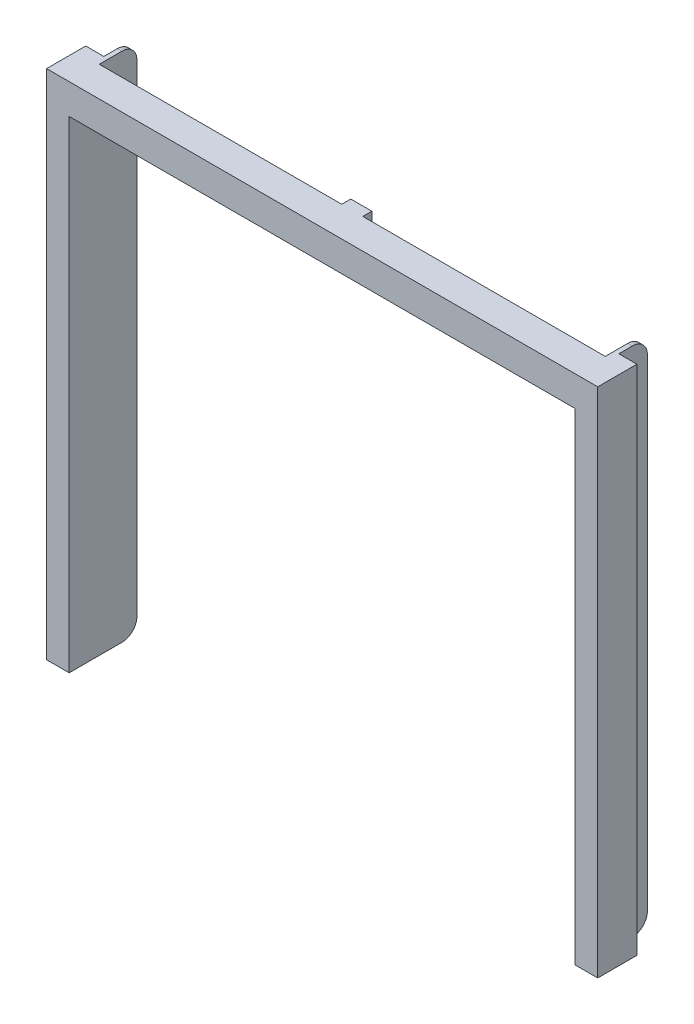
SolidWorks part; units mm, degrees
ref_plane "정면" through (0, 0, 0) normal (0, 0, 1) x (1, 0, 0)
ref_plane "윗면" through (0, 0, 0) normal (0, 1, 0) x (1, 0, 0)
ref_plane "우측면" through (0, 0, 0) normal (1, 0, 0) x (0, 0, -1)
sketch "스케치1" plane through (0, 0, 0) normal (0, 0, 1) x (1, 0, 0)
  line L0 (-318.5049, 0) -> (318.5049, 0) construction
  line L1 (0, 0) -> (0, -258.8265) construction
  line L2 (-168, 0) -> (168, 0)
  line L3 (-168, -20) -> (168, -20)
  line L4 (168, -20) -> (168, 0) construction
  line L5 (168, -20) -> (168, -340)
  line L6 (171, -340) -> (171, 0)
  line L7 (168, 0) -> (183, 0)
  line L8 (183, 0) -> (183, -340)
  line L9 (183, -340) -> (168, -340)
  line L10 (-168, -20) -> (-168, 0) construction
  line L11 (-183, -340) -> (-168, -340)
  line L12 (-183, 0) -> (-183, -340)
  line L13 (-168, 0) -> (-183, 0)
  line L14 (-171, -340) -> (-171, 0)
  line L15 (-168, -20) -> (-168, -340)
  line L16 (168, -20) -> (168, 0)
  line L17 (-168, -20) -> (-168, 0)
  point P14 (0, -20)
  dimension "D1" = 168
  dimension "D2" = 20
  dimension "D3" = 3
  dimension "D4" = 340
  dimension "D5" = 15
extrude "보스-돌출1" add sketch "스케치1" along normal blind 26 contours L3 L5 L9 L8 L7 L2 L13 L12 L11 L15
extrude "보스-돌출2" add sketch "스케치1<4>" against normal blind 19 contours L16 L5 L9 L6 L7 | L15 L17 L13 L14 L11 region at (-169.5, -170, 0) region at (169.5, -170, 0)
sketch "스케치1<4>" plane through (0, 0, 0) normal (0, 0, 1) x (1, 0, 0) same geometry as "스케치1"
fillet "필렛1" radius 10 4 edges at (-169.5, 0, -19) (169.5, 0, -19) (169.5, -340, -19) (-169.5, -340, -19)
sketch "스케치2" plane through (171, 0, 0) normal (1, 0, 0) x (0, 0, -1)
  line L0 (14, -340) -> (14, 0)
  line L1 (12, 0) -> (12, -340)
  line L4 (19, -330) -> (19, -10)
  line L5 (9, 0) -> (0, 0)
  line L6 (0, 0) -> (0, -340)
  line L7 (0, -340) -> (9, -340)
  line L8 (19, -330) -> (19, -10)
  line L9 (9, 0) -> (0, 0)
  line L10 (0, 0) -> (0, -340)
  line L11 (0, -340) -> (9, -340)
  arc A2 (19, -10) -> (9, 0) centre (9, -10) ccw
  arc A3 (9, -340) -> (19, -330) centre (9, -330) ccw
  arc A4 (19, -10) -> (9, 0) centre (9, -10) ccw
  arc A5 (9, -340) -> (19, -330) centre (9, -330) ccw
  dimension "D2" = 5
  dimension "D3" = 2
  dimension "D1" = 0
sketch "스케치3" plane through (168, 0, 0) normal (-1, 0, 0) x (0, 0, 1)
  line L0 (-12, 0) -> (-12, -340) construction
  line L1 (-14, -340) -> (-14, 0) construction
  line L2 (-12, 0) -> (-12, -340)
  line L3 (-14, -340) -> (-14, 0)
  line L4 (-19, -10) -> (-19, -330)
  line L5 (0, 0) -> (-9, 0)
  line L6 (0, -340) -> (0, 0)
  line L7 (-9, -340) -> (0, -340)
  line L8 (-19, -10) -> (-19, -330)
  line L9 (0, 0) -> (-9, 0)
  line L10 (0, -340) -> (0, 0)
  line L11 (-9, -340) -> (0, -340)
  arc A2 (-9, 0) -> (-19, -10) centre (-9, -10) ccw
  arc A3 (-19, -330) -> (-9, -340) centre (-9, -330) ccw
  arc A4 (-9, 0) -> (-19, -10) centre (-9, -10) ccw
  arc A5 (-19, -330) -> (-9, -340) centre (-9, -330) ccw
  dimension "D1" = 0
sketch "스케치5" plane through (0, 0, 0) normal (0, 1, 0) x (1, 0, 0)
  line L0 (-7, 0) -> (-7, -26)
  line L1 (7, 0) -> (7, -26)
  line L2 (-168, 0) -> (-168, -6)
  line L3 (-168, -6) -> (-7, -6)
  line L4 (7, -6) -> (168, -6)
  line L5 (168, -6) -> (168, 0)
  line L12 (-168, 0) -> (-168, 9)
  line L13 (-168, 9) -> (-171, 9)
  line L14 (-171, 9) -> (-171, 0)
  line L15 (-171, 0) -> (-183, 0)
  line L16 (-183, 0) -> (-183, -26)
  line L17 (-183, -26) -> (183, -26)
  line L18 (183, -26) -> (183, 0)
  line L19 (183, 0) -> (171, 0)
  line L20 (171, 0) -> (171, 9)
  line L21 (171, 9) -> (168, 9)
  line L22 (168, 9) -> (168, 0)
  line L23 (168, 0) -> (-168, 0)
  line L24 (-168, 0) -> (-168, 9)
  line L25 (-168, 9) -> (-171, 9)
  line L26 (-171, 9) -> (-171, 0)
  line L27 (-171, 0) -> (-183, 0)
  line L28 (-183, 0) -> (-183, -26)
  line L29 (-183, -26) -> (183, -26)
  line L30 (183, -26) -> (183, 0)
  line L31 (183, 0) -> (171, 0)
  line L32 (171, 0) -> (171, 9)
  line L33 (171, 9) -> (168, 9)
  line L34 (168, 9) -> (168, 0)
  line L35 (168, 0) -> (-168, 0)
  line M27 (168, 0) -> (-168, 0)
  dimension "D2" = 7
  dimension "D3" = 7
  dimension "D4" = 6
  dimension "D1" = 0
extrude "컷-돌출1" cut sketch "스케치5" against normal blind 52 contours L2 L3 L0 M27 | L4 L5 L1 M27 region at (-87.5, 0, 3) region at (87.5, 0, 3)
